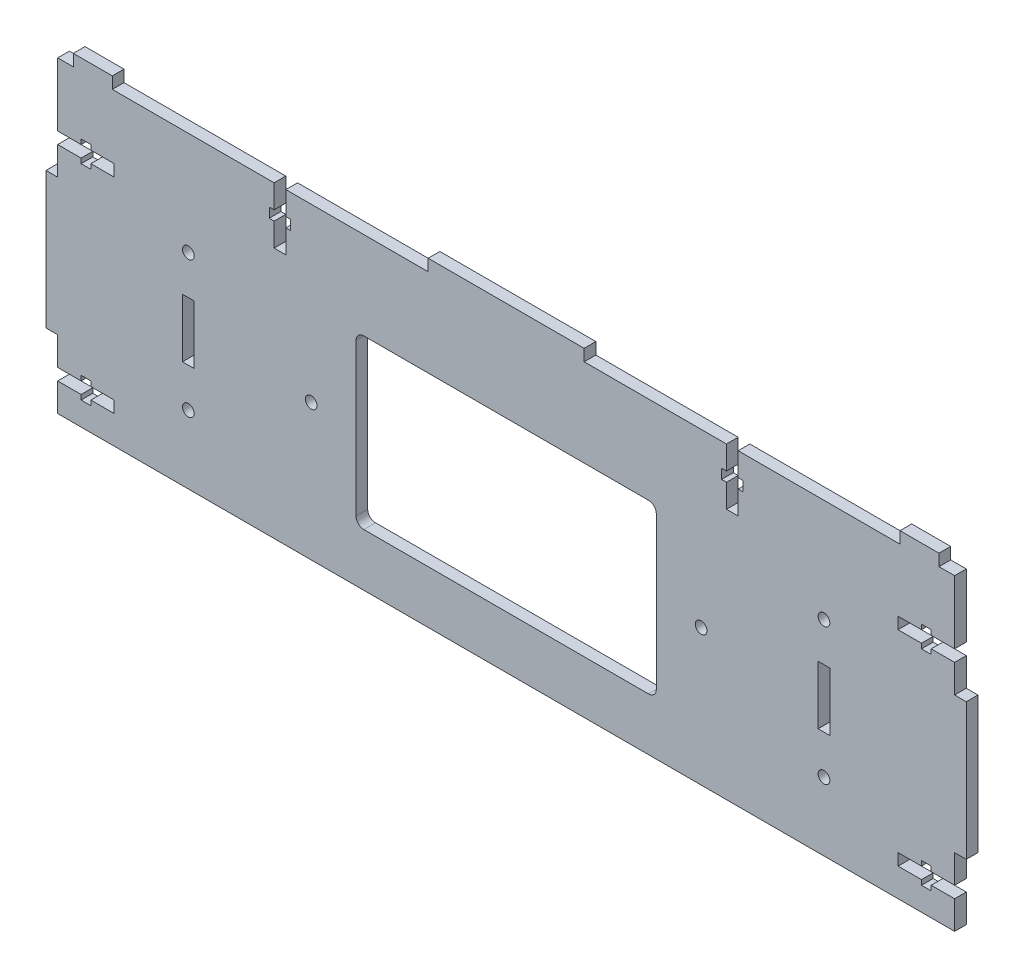
SolidWorks part; units mm, degrees
ref_plane "Спереди" through (0, 0, 0) normal (0, 0, 1) x (1, 0, 0)
ref_plane "Сверху" through (0, 0, 0) normal (0, 1, 0) x (1, 0, 0)
ref_plane "Справа" through (0, 0, 0) normal (1, 0, 0) x (0, 0, -1)
sketch "Эскиз1" plane through (0, 0, 0) normal (0, 0, 1) x (1, 0, 0)
  line L1 (0, 0) -> (230, 0)
  line L2 (0, 0) -> (0, 79)
  line L3 (0, 79) -> (230, 79)
  line L4 (230, 0) -> (230, 79)
  dimension "D1" = 79
  dimension "D2" = 230
extrude "Бобышка-Вытянуть1" add sketch "Эскиз1" along normal blind 3
sketch "Эскиз4" plane through (230, 0, 0) normal (1, 0, 0) x (0, 0, -1)
  line L0 (-3, 0) -> (-3, 79) construction
  line L1 (-3, 17.5) -> (0, 17.5)
  line L2 (-3, 17.5) -> (-3, 52.5)
  line L3 (-3, 52.5) -> (0, 52.5)
  line L4 (0, 17.5) -> (0, 52.5)
  line L5 (0, 0) -> (0, 79) construction
  point P8 (-3, 35)
  dimension "D1" = 35
  dimension "D2" = 35
extrude "Бобышка-Вытянуть2" add sketch "Эскиз4" along normal blind 3 and the other way blind 233
sketch "Эскиз2" plane through (0, 0, 3) normal (0, 0, 1) x (1, 0, 0)
  line L0 (230, 79) -> (0, 79) construction
  line L1 (0, 0) -> (230, 0) construction
  circle A0 centre (65, 35) radius 1.5
  circle A1 centre (165, 35) radius 1.5
  point P6 (115, 79)
  dimension "D1" = 3
  dimension "D2" = 100
  dimension "D3" = 50
  dimension "D4" = 35
extrude "Вырез-Вытянуть1" cut sketch "Эскиз2" against normal blind 3
sketch "Эскиз3" plane through (0, 0, 3) normal (0, 0, 1) x (1, 0, 0)
  line L0 (0, 0) -> (230, 0) construction
  circle A0 centre (33.5, 52.5) radius 1.5
  circle A1 centre (196.5, 52.5) radius 1.5
  circle A2 centre (196.5, 17.5) radius 1.5
  circle A3 centre (33.5, 17.5) radius 1.5
  point P12 (115, 0)
  dimension "D1" = 3
  dimension "D2" = 163
  dimension "D3" = 35
  dimension "D4" = 17.5
  dimension "D5" = 81.5
extrude "Вырез-Вытянуть2" cut sketch "Эскиз3" against normal blind 3
sketch "Эскиз5" plane through (0, 0, 3) normal (0, 0, 1) x (1, 0, 0)
  line L0 (0, 0) -> (230, 0) construction
  line L1 (32, 27.5) -> (35, 27.5)
  line L2 (32, 27.5) -> (32, 42.5)
  line L3 (32, 42.5) -> (35, 42.5)
  line L4 (35, 27.5) -> (35, 42.5)
  line L5 (32, 27.5) -> (35, 42.5) construction
  line L6 (32, 42.5) -> (35, 27.5) construction
  line L7 (195, 27.5) -> (198, 27.5)
  line L8 (195, 27.5) -> (195, 42.5)
  line L9 (195, 42.5) -> (198, 42.5)
  line L10 (198, 27.5) -> (198, 42.5)
  line L11 (195, 27.5) -> (198, 42.5) construction
  line L12 (195, 42.5) -> (198, 27.5) construction
  circle A0 centre (33.5, 17.5) radius 1.5 construction
  point P0 (33.5, 35)
  point P5 (196.5, 35)
  point P19 (115, 0)
  dimension "D1" = 163
  dimension "D2" = 3
  dimension "D3" = 15
  dimension "D4" = 17.5
  dimension "D5" = 81.5
extrude "Вырез-Вытянуть3" cut sketch "Эскиз5" against normal blind 3
sketch "Эскиз6" plane through (0, 0, 3) normal (0, 0, 1) x (1, 0, 0)
  line L0 (0, 10.25) -> (6, 10.25)
  line L1 (6, 10.25) -> (6, 11.5)
  line L2 (6, 11.5) -> (8.5, 11.5)
  line L3 (8.5, 11.5) -> (8.5, 10.25)
  line L4 (8.5, 10.25) -> (14.5, 10.25)
  line L5 (14.5, 10.25) -> (14.5, 7.25)
  line L6 (14.5, 7.25) -> (8.5, 7.25)
  line L7 (8.5, 7.25) -> (8.5, 6)
  line L8 (8.5, 6) -> (6, 6)
  line L9 (6, 6) -> (6, 7.25)
  line L10 (6, 7.25) -> (0, 7.25)
  line L11 (0, 7.25) -> (0, 10.25)
  line L12 (0, 17.5) -> (0, 0) construction
  line L13 (-3, 35) -> (18.5443, 35) construction
  line L14 (-3, 52.5) -> (-3, 17.5) construction
  line L15 (115, 79) -> (115, 45.2573) construction
  line L16 (230, 79) -> (0, 79) construction
  line L17 (230, 7.25) -> (230, 10.25)
  line L18 (224, 7.25) -> (230, 7.25)
  line L19 (224, 6) -> (224, 7.25)
  line L20 (221.5, 6) -> (224, 6)
  line L21 (221.5, 7.25) -> (221.5, 6)
  line L22 (215.5, 7.25) -> (221.5, 7.25)
  line L23 (215.5, 10.25) -> (215.5, 7.25)
  line L24 (221.5, 10.25) -> (215.5, 10.25)
  line L25 (221.5, 11.5) -> (221.5, 10.25)
  line L26 (224, 11.5) -> (221.5, 11.5)
  line L27 (224, 10.25) -> (224, 11.5)
  line L28 (230, 10.25) -> (224, 10.25)
  line L29 (230, 59.75) -> (224, 59.75)
  line L30 (224, 59.75) -> (224, 58.5)
  line L31 (224, 58.5) -> (221.5, 58.5)
  line L32 (221.5, 58.5) -> (221.5, 59.75)
  line L33 (221.5, 59.75) -> (215.5, 59.75)
  line L34 (215.5, 59.75) -> (215.5, 62.75)
  line L35 (215.5, 62.75) -> (221.5, 62.75)
  line L36 (221.5, 62.75) -> (221.5, 64)
  line L37 (221.5, 64) -> (224, 64)
  line L38 (224, 64) -> (224, 62.75)
  line L39 (224, 62.75) -> (230, 62.75)
  line L40 (230, 62.75) -> (230, 59.75)
  line L41 (0, 62.75) -> (0, 59.75)
  line L42 (6, 62.75) -> (0, 62.75)
  line L43 (6, 64) -> (6, 62.75)
  line L44 (8.5, 64) -> (6, 64)
  line L45 (8.5, 62.75) -> (8.5, 64)
  line L46 (14.5, 62.75) -> (8.5, 62.75)
  line L47 (14.5, 59.75) -> (14.5, 62.75)
  line L48 (8.5, 59.75) -> (14.5, 59.75)
  line L49 (8.5, 58.5) -> (8.5, 59.75)
  line L50 (6, 58.5) -> (8.5, 58.5)
  line L51 (6, 59.75) -> (6, 58.5)
  line L52 (0, 59.75) -> (6, 59.75)
  point P12 (0, 8.75)
  point P15 (0, 8.75)
  dimension "D1" = 6
  dimension "D2" = 5.5
  dimension "D3" = 3
  dimension "D4" = 2.5
extrude "Вырез-Вытянуть4" cut sketch "Эскиз6" against normal blind 3
sketch "Эскиз8" plane through (0, 79, 0) normal (0, 1, 0) x (1, 0, 0)
  line L0 (230, -3) -> (0, -3) construction
  line L1 (216, -3) -> (226, -3)
  line L2 (216, -3) -> (216, 0)
  line L3 (216, 0) -> (226, 0)
  line L4 (226, -3) -> (226, 0)
  line L5 (230, 0) -> (0, 0) construction
  line L6 (115, 0) -> (115, -9.1014) construction
  line L7 (4, -3) -> (4, 0)
  line L8 (14, 0) -> (4, 0)
  line L9 (14, -3) -> (14, 0)
  line L10 (14, -3) -> (4, -3)
  dimension "D1" = 10
  dimension "D2" = 7
extrude "Бобышка-Вытянуть3" add sketch "Эскиз8" along normal blind 3
sketch "Эскиз9" plane through (0, 79, 0) normal (0, 1, 0) x (1, 0, 0)
  line L0 (216, -3) -> (14, -3) construction
  line L1 (95, -3) -> (135, -3)
  line L2 (95, -3) -> (95, 0)
  line L3 (95, 0) -> (135, 0)
  line L4 (135, -3) -> (135, 0)
  line L5 (216, 0) -> (14, 0) construction
  point P8 (115, -3)
  point P9 (115, -3)
  dimension "D1" = 40
extrude "Бобышка-Вытянуть4" add sketch "Эскиз9" along normal blind 3
sketch "Эскиз10" plane through (0, 0, 3) normal (0, 0, 1) x (1, 0, 0)
  line L0 (55.5, 79) -> (55.5, 73)
  line L1 (55.5, 73) -> (54.25, 73)
  line L2 (54.25, 73) -> (54.25, 70.5)
  line L3 (54.25, 70.5) -> (55.5, 70.5)
  line L4 (55.5, 70.5) -> (55.5, 64.5)
  line L5 (55.5, 64.5) -> (58.5, 64.5)
  line L6 (58.5, 64.5) -> (58.5, 70.5)
  line L7 (58.5, 70.5) -> (59.75, 70.5)
  line L8 (59.75, 70.5) -> (59.75, 73)
  line L9 (59.75, 73) -> (58.5, 73)
  line L10 (58.5, 73) -> (58.5, 79)
  line L11 (58.5, 79) -> (55.5, 79)
  line L12 (95, 79) -> (14, 79) construction
  line L13 (115, 82) -> (115, 64.5) construction
  line L14 (95, 82) -> (135, 82) construction
  line L15 (171.5, 79) -> (174.5, 79)
  line L16 (171.5, 73) -> (171.5, 79)
  line L17 (170.25, 73) -> (171.5, 73)
  line L18 (170.25, 70.5) -> (170.25, 73)
  line L19 (171.5, 70.5) -> (170.25, 70.5)
  line L20 (171.5, 64.5) -> (171.5, 70.5)
  line L21 (174.5, 64.5) -> (171.5, 64.5)
  line L22 (174.5, 70.5) -> (174.5, 64.5)
  line L23 (175.75, 70.5) -> (174.5, 70.5)
  line L24 (175.75, 73) -> (175.75, 70.5)
  line L25 (174.5, 73) -> (175.75, 73)
  line L26 (174.5, 79) -> (174.5, 73)
  point P17 (57, 79)
  dimension "D1" = 6
  dimension "D2" = 3
  dimension "D3" = 5.5
  dimension "D4" = 2.5
  dimension "D5" = 60
extrude "Вырез-Вытянуть5" cut sketch "Эскиз10" against normal blind 3
sketch "Эскиз11" plane through (0, 0, 3) normal (0, 0, 1) x (1, 0, 0)
  line L0 (0, 0) -> (230, 0) construction
  line L1 (78.5, 56.5) -> (151.5, 56.5)
  line L2 (76.5, 54.5) -> (76.5, 15.5)
  line L3 (78.5, 13.5) -> (151.5, 13.5)
  line L4 (153.5, 54.5) -> (153.5, 15.5)
  line L5 (76.5, 56.5) -> (153.5, 13.5) construction
  line L6 (76.5, 13.5) -> (153.5, 56.5) construction
  line L7 (-3, 52.5) -> (-3, 17.5) construction
  arc A1 (151.5, 56.5) -> (153.5, 54.5) centre (151.5, 54.5) cw
  arc A2 (153.5, 15.5) -> (151.5, 13.5) centre (151.5, 15.5) cw
  arc A3 (78.5, 13.5) -> (76.5, 15.5) centre (78.5, 15.5) cw
  arc A4 (76.5, 54.5) -> (78.5, 56.5) centre (78.5, 54.5) cw
  point P0 (115, 35)
  point P5 (0, 0)
  point P8 (115, 0)
  point P9 (0, 0)
  point P12 (0, 0)
  point P15 (-3, 35)
  dimension "D3" = 2
  dimension "D1" = 77
  dimension "D2" = 43
extrude "Вырез-Вытянуть6" cut sketch "Эскиз11" against normal blind 3
